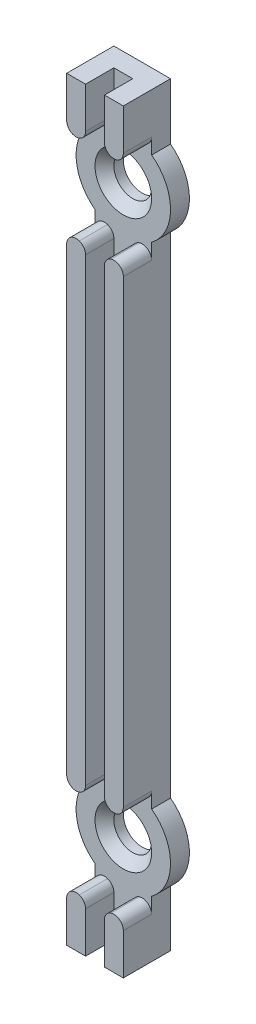
SolidWorks part; units mm, degrees
ref_plane "Plan de face" through (0, 0, 0) normal (0, 0, 1) x (1, 0, 0)
ref_plane "Plan de dessus" through (0, 0, 0) normal (0, 1, 0) x (1, 0, 0)
ref_plane "Plan de droite" through (0, 0, 0) normal (1, 0, 0) x (0, 0, -1)
sketch "Esquisse1" plane through (0, 0, 0) normal (0, 0, 1) x (1, 0, 0)
  line L1 (-9.1054, 40.2626) -> (-3.1054, 40.2626)
  line L2 (-9.1054, 40.2626) -> (-9.1054, -39.7374)
  line L3 (-9.1054, -39.7374) -> (-3.1054, -39.7374)
  line L4 (-3.1054, 40.2626) -> (-3.1054, -39.7374)
  circle A0 centre (-6.1054, -29.7374) radius 5
  circle A1 centre (-6.1054, 30.2626) radius 5
  circle A2 centre (-6.1054, -29.7374) radius 2
  circle A3 centre (-6.1054, 30.2626) radius 2
  dimension "D5" = 10
  dimension "D6" = 10
  dimension "D7" = 4
  dimension "D8" = 4
  dimension "D1" = 80
  dimension "D2" = 6
  dimension "D3" = 70
  dimension "D4" = 10
extrude "Boss.-Extru.1" add sketch "Esquisse1" along normal blind 5 contours A0 L2 L3 L4 | L2 A0 | L4 A0 L2 A2 | L4 A0 | L2 A1 | A1 L2 A0 L4 | A1 L4 L1 L2 | L4 A1 L2 A3 | L4 A1 | L4 L3 L2 L1 region at (-6.1054, 37.5951, 0) region at (-6.1054, 35.146, 0) region at (-9.9209, 30.2626, 0) region at (-2.2898, 30.2626, 0) region at (-6.1054, 0.2626, 0) region at (-6.1054, -24.854, 0) region at (-9.9209, -29.7374, 0) region at (-2.2898, -29.7374, 0) region at (-6.1054, -37.07, 0)
sketch "Esquisse2" plane through (0, 0, 5) normal (0, 0, 1) x (1, 0, 0)
  line L0 (-9.1054, 40.2626) -> (-3.1054, 40.2626) construction
  line L1 (-7.1054, 40.2626) -> (-5.1054, 40.2626)
  line L2 (-7.1054, 40.2626) -> (-7.1054, -39.7374)
  line L3 (-7.1054, -39.7374) -> (-5.1054, -39.7374)
  line L4 (-5.1054, 40.2626) -> (-5.1054, -39.7374)
  line L5 (-9.1054, -39.7374) -> (-3.1054, -39.7374) construction
  circle A0 centre (-6.1054, 30.2626) radius 5
  circle A1 centre (-6.1054, -29.7374) radius 5
  arc M2 (-3.1054, 26.2626) -> (-3.1054, 34.2626) centre (-6.1054, 30.2626) ccw
  line M4 (-3.1054, 40.2626) -> (-9.1054, 40.2626)
  arc M6 (-9.1054, 34.2626) -> (-9.1054, 26.2626) centre (-6.1054, 30.2626) ccw
  arc M8 (-9.1054, -25.7374) -> (-9.1054, -33.7374) centre (-6.1054, -29.7374) ccw
  line M10 (-9.1054, -39.7374) -> (-3.1054, -39.7374)
  arc M12 (-3.1054, -33.7374) -> (-3.1054, -25.7374) centre (-6.1054, -29.7374) ccw
  dimension "D3" = 10
  dimension "D4" = 10
  dimension "D1" = 2
  dimension "D2" = 2
extrude "Enlèv. mat.-Extru.1" cut sketch "Esquisse2" against normal blind 3 contours A1 L4 A0 L2 | A1 L4 M12 | L2 A1 M8 | L4 A1 L2 | A1 L2 L4 M10 | A0 L4 M2 | L2 A0 M6 | L4 A0 L2 | A0 L4 L2 M4 region at (-6.1054, 37.7457, 5) region at (-6.1054, 30.2626, 5) region at (-8.7772, 30.2626, 5) region at (-3.4335, 30.2626, 5) region at (-6.1054, 0.2626, 5) region at (-6.1054, -29.7374, 5) region at (-8.7772, -29.7374, 5) region at (-3.4335, -29.7374, 5) region at (-6.1054, -37.2206, 5)
sketch "Esquisse3" plane through (0, 0, 2) normal (0, 0, 1) x (1, 0, 0)
  circle A0 centre (-6.1054, 30.2626) radius 2
  circle A1 centre (-6.1054, -29.7374) radius 2
  dimension "D1" = 4
  dimension "D2" = 4
extrude "Enlèv. mat.-Extru.2" cut sketch "Esquisse3" against normal through all both and the other way through all
chamfer "Chanfrein1" distance 1 angle 45 2 edges at (-4.1054, -29.7374, 2) (-4.1054, 30.2626, 2)
fillet "Congé1" radius 1 16 edges at (-3.1054, 34.2626, 3.5) (-5.1054, 35.1616, 3.5) (-7.1054, 35.1616, 3.5) (-9.1054, 34.2626, 3.5) (-3.1054, 26.2626, 3.5) (-5.1054, 25.3636, 3.5) (-9.1054, 26.2626, 3.5) (-7.1054, 25.3636, 3.5) (-5.1054, -24.8384, 3.5) (-7.1054, -34.6364, 3.5) (-5.1054, -34.6364, 3.5) (-7.1054, -24.8384, 3.5) (-9.1054, -33.7374, 3.5) (-3.1054, -25.7374, 3.5) (-9.1054, -25.7374, 3.5) (-3.1054, -33.7374, 3.5)
